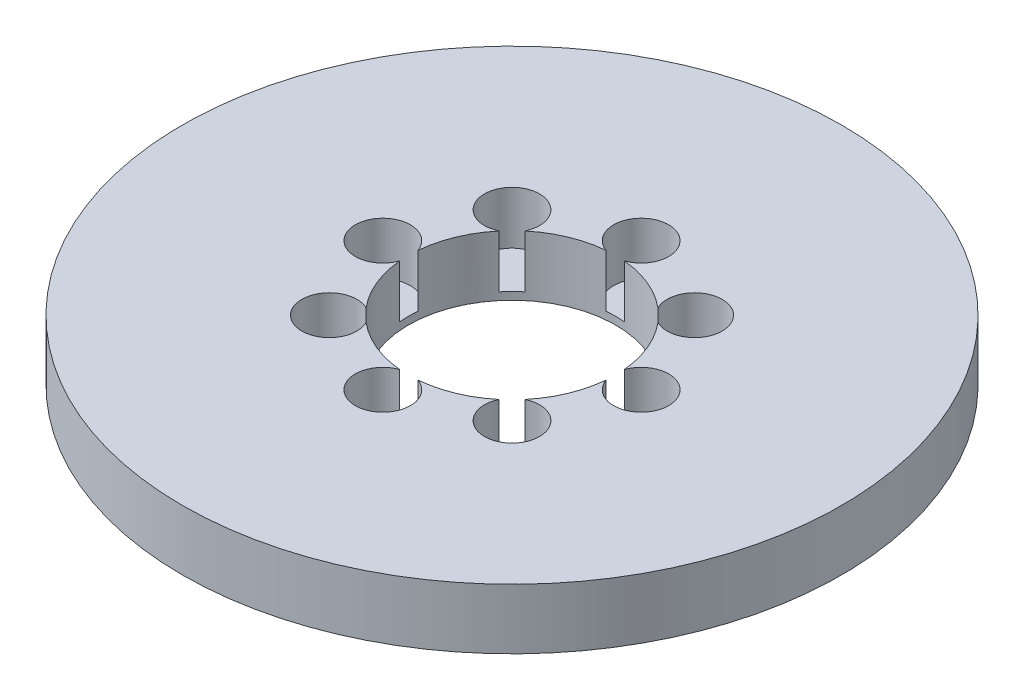
SolidWorks part; units mm, degrees
ref_plane "Front Plane" through (0, 0, 0) normal (0, 0, 1) x (1, 0, 0)
ref_plane "Top Plane" through (0, 0, 0) normal (0, 1, 0) x (1, 0, 0)
ref_plane "Right Plane" through (0, 0, 0) normal (1, 0, 0) x (0, 0, -1)
sketch "Sketch1" plane through (0, 0, 0) normal (0, 1, 0) x (1, 0, 0)
  circle A0 centre (0, 0) radius 87.5
  dimension "FLANGE_OD" = 175
extrude "Boss-Extrude1" add sketch "Sketch1" along normal blind 16
sketch "Sketch2" plane through (0, 0, 0) normal (0, 1, 0) x (1, 0, 0)
  circle A0 centre (0, 0) radius 27.5
  dimension "BORE_D" = 55
extrude "Cut-Extrude1" cut sketch "Sketch2" along normal through all
sketch "Sketch3" plane through (0, 16, 0) normal (0, 1, 0) x (1, 0, 0)
  circle A0 centre (0, 0) radius 34.2892 construction
  circle A1 centre (-34.2892, 0) radius 7.3078
  dimension "BOLT_D" = 14.6156
  dimension "BOLT_PCD" = 68.5784
extrude "Cut-Extrude2" cut sketch "Sketch3" against normal blind 13.9942
pattern_circular "CirPattern1" count 8 over 360 about axis through (0, 0, 0) along (0, 1, 0) of "Cut-Extrude2"
